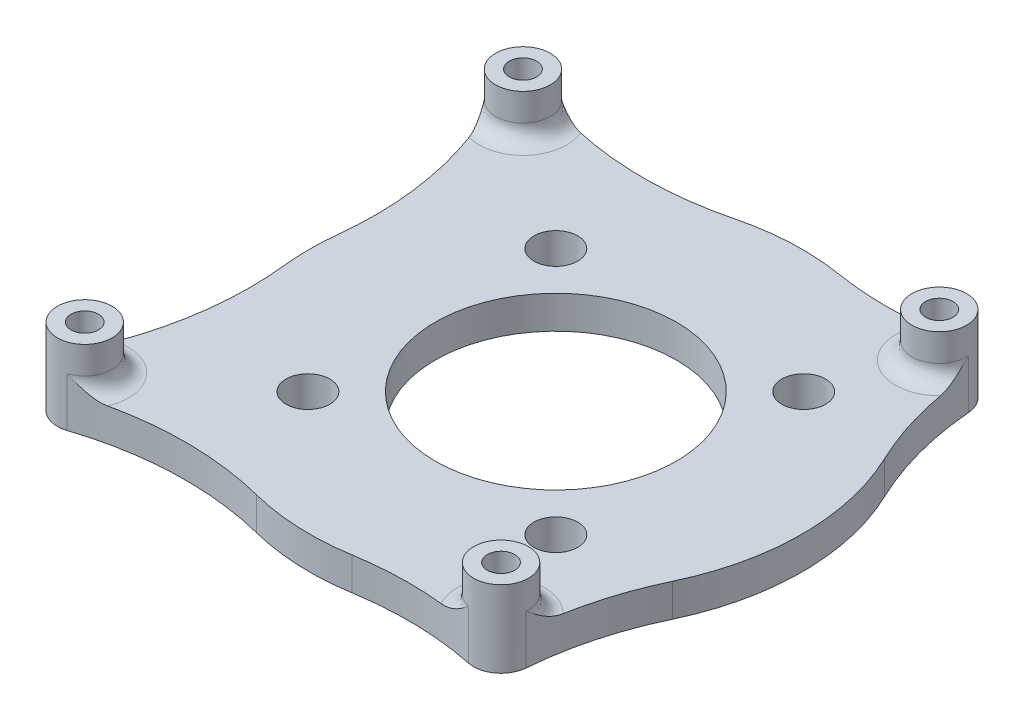
SolidWorks part; units mm, degrees
ref_plane "Front Plane" through (0, 0, 0) normal (0, 0, 1) x (1, 0, 0)
ref_plane "Top Plane" through (0, 0, 0) normal (0, 1, 0) x (1, 0, 0)
ref_plane "Right Plane" through (0, 0, 0) normal (1, 0, 0) x (0, 0, -1)
sketch "Sketch1" plane through (0, 0, 0) normal (0, 1, 0) x (1, 0, 0)
  line L0 (-23, 0) -> (15, 0) construction
  line L1 (-23, 20) -> (15, 20) construction
  line L2 (-23, 20) -> (-23, -20) construction
  line L3 (-23, -20) -> (15, -20) construction
  line L4 (15, 20) -> (15, -20) construction
  line L5 (-4, 20) -> (-4, -20) construction
  line L6 (0, 20) -> (0, -20) construction
  line L7 (-23, 20) -> (0, 0) construction
  line L8 (0, 0) -> (-23, -20) construction
  line L9 (15, 20) -> (0, 0) construction
  line L10 (0, 0) -> (15, -20) construction
  line L11 (-21.3596, 21.8865) -> (-15.233, 16.5591)
  line L12 (-11.3137, 11.3137) -> (0, 0) construction
  line L13 (15.4164, -16.3885) -> (17, -18.5)
  line L14 (17, 18.5) -> (15.4164, 16.3885)
  line L15 (-24.6404, 18.1135) -> (-18.5139, 12.7861)
  line L16 (2, 1.5) -> (17, -18.5) construction
  line L18 (13, 21.5) -> (11.4164, 19.3885)
  line L19 (11.4164, -19.3885) -> (13, -21.5)
  line L20 (-21.3596, 21.8865) -> (1.6404, 1.8865) construction
  line L22 (-24.6404, 18.1135) -> (-1.6404, -1.8865) construction
  line L23 (17, 18.5) -> (2, -1.5) construction
  line L24 (13, 21.5) -> (-2, 1.5) construction
  line L29 (-15.233, -16.5591) -> (-26.0573, -25.9715)
  line L31 (-18.5139, -12.7861) -> (-29.3382, -22.1985)
  circle A0 centre (0, 0) radius 16 construction
  circle A1 centre (-11.3137, 11.3137) radius 2
  circle A2 centre (11.3137, 11.3137) radius 2
  circle A3 centre (11.3137, -11.3137) radius 2
  circle A4 centre (-11.3137, -11.3137) radius 2
  circle A5 centre (0, 0) radius 11
  circle A6 centre (15, 20) radius 2.5
  circle A7 centre (-23, 20) radius 2.5
  circle A8 centre (-23, -20) radius 2.5
  circle A9 centre (15, -20) radius 2.5
  circle A10 centre (-23, 20) radius 1.75 construction
  circle A11 centre (-23, 20) radius 1.25
  circle A12 centre (15, 20) radius 1.75 construction
  circle A13 centre (15, 20) radius 1.25
  circle A14 centre (-23, -20) radius 1.75 construction
  circle A15 centre (-23, -20) radius 1.25
  circle A16 centre (15, -20) radius 1.75 construction
  circle A17 centre (15, -20) radius 1.25
  circle A19 centre (0, 0) radius 22.5
  point P14 (0, 0)
  dimension "D1" = 32
  dimension "D2" = 4
  dimension "D8" = 5
  dimension "D9" = 3.5
  dimension "D10" = 2.5
  dimension "D4" = 5
  dimension "D5" = 23
  dimension "D6" = 15
  dimension "D7" = 20
  dimension "D14" = 2.5
  dimension "D15" = 2.5
  dimension "D16" = 2.5
  dimension "D11" = 45
  dimension "D12" = 2.5
  dimension "D13" = 2.5
  dimension "D3" = 4
extrude "Boss-Extrude1" add sketch "Sketch1" along normal blind 3 contours A19 A1 A2 A3 A4 A5 | A19 L11 A7 L15 | A7 A11 | A6 A13 | A19 L14 A6 L18 | A19 L19 A9 L13 | A9 A17 | A19 L31 A8 L29 | A8 A15 | A19 L14 A6 | A19 A9 L13 region at (-19.2502, 0, -16.7393) region at (-20.7894, 0, -21.0072) region at (-2.3083, 0, -21.7414) region at (12.2573, 0, -19.5703) region at (15.7682, 0, -22.3046) region at (15.3554, 0, -17.2467) region at (-19.2502, 0, 16.7393) region at (-21.9928, 0, 17.7894) region at (12.2573, 0, 19.5703) region at (15.3554, 0, 17.2467) region at (12.5951, 0, 19.6564)
fillet "Fillet1" radius 30 8 edges at (11.4164, 1.5, -19.3885) (15.4164, 1.5, -16.3885) (15.4164, 1.5, 16.3885) (11.4164, 1.5, 19.3885) (-15.233, 1.5, 16.5591) (-15.233, 1.5, -16.5591) (-18.5139, 1.5, 12.7861) (-18.5139, 1.5, -12.7861)
sketch "Sketch2" plane through (0, 3, 0) normal (0, 1, 0) x (1, 0, 0)
  circle A0 centre (-23, 20) radius 2.5
  circle A1 centre (15, 20) radius 2.5
  circle A2 centre (15, -20) radius 2.5
  circle A3 centre (-23, -20) radius 2.5
  circle A4 centre (-23, 20) radius 1.25
  circle A5 centre (-23, 20) radius 1.25 construction
  circle A6 centre (15, 20) radius 1.25 construction
  circle A7 centre (-23, -20) radius 1.25 construction
  circle A8 centre (15, 20) radius 1.25
  circle A9 centre (-23, -20) radius 1.25
  circle A10 centre (15, -20) radius 1.25 construction
  circle A11 centre (15, -20) radius 1.25
  dimension "D1" = 5
extrude "Boss-Extrude2" add sketch "Sketch2" along normal blind 4
fillet "Fillet2" radius 1.5 4 edges at (-21.1135, 3, -18.3596) (-21.1135, 3, 18.3596) (13.5, 3, -18) (13.5, 3, 18)
sketch "Sketch3" plane through (0, 0, 0) normal (0, -1, 0) x (1, 0, 0)
  circle A1 centre (-23, -20) radius 1.75 construction
  circle A2 centre (15, -20) radius 1.75 construction
  circle A3 centre (15, 20) radius 1.75 construction
  circle A4 centre (-23, 20) radius 1.75 construction
  circle A5 centre (-23, -20) radius 1.75
  circle A6 centre (15, -20) radius 1.75
  circle A7 centre (15, 20) radius 1.75
  circle A8 centre (-23, 20) radius 1.75
extrude "Cut-Extrude1" cut sketch "Sketch3" against normal blind 3.5
equation "\"Ns\" = 33"
equation "\"Np\" = 45"
equation "\"Nr\" = 123"
equation "\"module\" = 0.5"
equation "\"num_planet\" = 3"
equation "\"pressure angle\" = 20.0"
equation "\"pressure_angle\" = 20.0"
equation "\"h_a\" = 0.5"
equation "\"h_b\" = 0.625"
equation "\"clr_tip_root\" = 0.125"
equation "\"h_f\" = 0.625"
equation "\"planet_bore\" = 10"
equation "\"motor_OD\" = 72"
equation "\"motor_height\" = 27"
equation "\"bearing_ID\" = 50"
equation "\"bearing_OD\" = 65"
equation "\"bearing_height\" = 7"
equation "\"clearance_planet\" = 1.5"
equation "\"sec_carrier_thickness\" = 5"
equation "\"sun_coupler_hub_thickness\" = 4"
equation "\"clearance_sun_coupler_sec_carrier\" = 1.5"
equation "\"clearance_motor_and_case\" = 5"
equation "\"case_mounting_surface_height\" = 4"
equation "\"Motor_case_thickness\" = 2.5"
equation "\"Motor_case_ID\" = 82"
equation "\"motor_case_OD_base\" = 87.0"
equation "\"case_mounting_hole_dia\" = 3"
equation "\"case_mounting_hole_shift\" = 1.0"
equation "\"case_mounting_PCD\" = 89.0"
equation "\"case_mounting_hole_allen_socket_dia\" = 5.5"
equation "\"clearance_case_mount_holes_shell_thickness\" = 1"
equation "\"Motor_case_OD_max\" = 96.5"
equation "\"base_plate_thickness\" = 4"
equation "\"dp_s\" = 16.5"
equation "\"db_s\" = 15.50492824296749"
equation "\"fw_s_calc\" = 1.2595130854287364"
equation "\"alpha_s\" = 0.8539582918412449"
equation "\"beta_s\" = 3.7466288708629643"
equation "\"dp_p\" = 22.5"
equation "\"db_p\" = 21.14308396768294"
equation "\"fw_p\" = 8.0"
equation "\"alpha_p\" = 0.8539582918412307"
equation "\"beta_p\" = 2.2920834163175385"
equation "\"dp_r\" = 61.5"
equation "\"db_r\" = 57.79109617833337"
equation "\"fw_r\" = 8.0"
equation "\"alpha_r\" = 0.8539582918412414"
equation "\"beta_r\" = 3.171331217828824"
equation "\"case_dist\" = 6.5"
equation "\"bearing mount thickness\" = 8"
equation "\"output_mounting_PCD\" = 73"
equation "\"carrier_PCD\" = 39.0"
equation "\"motor_mount_hole_PCD\" = 32"
equation "\"motor_mount_hole_dia\" = 4"
equation "\"motor_mount_hole_num\" = 4"
equation "\"motor_output_hole_PCD\" = 22"
equation "\"motor_output_hole_dia\" = 3"
equation "\"motor_output_hole_num\" = 4"
equation "\"motor_output_hole_CSK_OD\" = 6"
equation "\"motor_output_hole_CSK_head_height\" = 1.5"
equation "\"output_mounting_nut_thickness\" = 3.2"
equation "\"output_mounting_nut_depth\" = 3"
equation "\"output_mounting_nut_wrench_size\" = 7"
equation "\"output_mounting_hole_dia\" = 4"
equation "\"case_mounting_bolt_depth\" = 4.5"
equation "\"case_mounting_wrench_size\" = 5.5"
equation "\"case_mounting_nut_clearance\" = 2"
equation "\"case_mounting_nut_thickness\" = 2.4"
equation "\"central_hole_offset_from_motor_mount_PCD\" = 5"
equation "\"wire_slot_dist_from_center\" = 30"
equation "\"wire_slot_length\" = 10"
equation "\"wire_slot_radius\" = 2.5"
equation "\"driver_upper_holes_dist_from_center\" = 23"
equation "\"driver_lower_holes_dist_from_center\" = 15"
equation "\"driver_side_holes_dist_from_center\" = 20"
equation "\"driver_mount_holes_dia\" = 2.5"
equation "\"driver_mount_inserts_OD\" = 3.5"
equation "\"driver_mount_thickness\" = 1.5"
equation "\"driver_mount_height\" = 4"
equation "\"air_flow_hole_offset\" = 3"
equation "\"ring_radial_thickness\" = 5"
equation "\"ring_OD\" = 71.5"
equation "\"ring_to_chamfer_clearance\" = 2"
equation "\"Motor_case_OD_base_to_chamfer\" = 5"
equation "\"pattern_offset_from_motor_case_OD_base\" = 3"
equation "\"pattern_bulge_dia\" = 3"
equation "\"pattern_num_bulge\" = 18"
equation "\"pattern_depth\" = 2"
equation "\"planet_pin_bolt_dia\" = 5"
equation "\"planet_pin_socket_head_dia\" = 8.5"
equation "\"planet_shaft_dia\" = 8"
equation "\"planet_pin_bolt_wrench_size\" = 8"
equation "\"planet_shaft_step_offset\" = 1"
equation "\"planet_bearing_OD\" = 12"
equation "\"planet_bearing_width\" = 3.5"
equation "\"carrier_trapezoidal_support_sun_offset\" = 5"
equation "\"carrier_trapezoidal_support_hole_PCD_offset_bearing_ID\" = 4"
equation "\"carrier_trapezoidal_support_hole_dia\" = 3"
equation "\"carrier_trapezoidal_support_hole_socket_head_dia\" = 5.5"
equation "\"carrier_trapezoidal_support_hole_wrench_size\" = 5.5"
equation "\"carrier_bearing_step_width\" = 1.5"
equation "\"standard_clearance_1_5mm\" = 1.5"
equation "\"standard_fillet_1_5mm\" = 1.5"
equation "\"sun_shaft_bearing_OD\" = 16"
equation "\"sun_shaft_bearing_width\" = 5"
equation "\"sun_shaft_bearing_ID\" = 8"
equation "\"standard_bearing_insertion_chamfer\" = 0.5"
equation "\"sun_hub_dia\" = 31.0"
equation "\"sun_central_bolt_dia\" = 5"
equation "\"sun_central_bolt_socket_head_dia\" = 8.5"
equation "\"fw_s_used\" = 16.0"
equation "\"bearing_retainer_thickness\" = 2"
equation "\"tight_clearance_3DP\" = 0.4"
equation "\"loose_clearance_3DP\" = 0.8"
equation "\"D1@Sketch1\"= \"motor_mount_hole_PCD\""
equation "\"D2@Sketch1\"= \"motor_mount_hole_dia\""
equation "\"D3@Sketch1\"= \"motor_mount_hole_num\""
equation "\"D4@Sketch1\"= \"central_hole_offset_from_motor_mount_PCD\""
equation "\"D5@Sketch1\"= \"driver_upper_holes_dist_from_center\""
equation "\"D6@Sketch1\"= \"driver_lower_holes_dist_from_center\""
equation "\"D7@Sketch1\"= \"driver_side_holes_dist_from_center\""
equation "\"D8@Sketch1\"= \"driver_mount_inserts_OD\" + \"driver_mount_thickness\""
equation "\"D9@Sketch1\"= \"driver_mount_inserts_OD\""
equation "\"D10@Sketch1\"= \"driver_mount_holes_dia\""
equation "\"D13@Sketch1\"=(\"driver_mount_inserts_OD\" + \"driver_mount_thickness\")/2"
equation "\"D12@Sketch1\"=(\"driver_mount_inserts_OD\" + \"driver_mount_thickness\")/2"
equation "\"D14@Sketch1\"=(\"driver_mount_inserts_OD\" + \"driver_mount_thickness\")/2"
equation "\"D15@Sketch1\"=(\"driver_mount_inserts_OD\" + \"driver_mount_thickness\")/2"
equation "\"D16@Sketch1\"=(\"driver_mount_inserts_OD\" + \"driver_mount_thickness\")/2"
equation "\"D1@Boss-Extrude1\"=\"standard_clearance_1_5mm\"*2"
equation "\"D1@Sketch2\"= \"driver_mount_inserts_OD\" + \"driver_mount_thickness\""
equation "\"D1@Boss-Extrude2\"= \"driver_mount_height\""
equation "\"D1@Fillet2\"= \"standard_fillet_1_5mm\""
equation "\"D1@Cut-Extrude1\"= \"driver_mount_inserts_OD\""
equation "\"Np_b\"= 53"
equation "\"Np_s\"= 34"
equation "\"Nr_b\"= 125"
equation "\"Nr_s\"= 115"
equation "\"alpha_p_b\"= 0.8539582918412343"
equation "\"alpha_p_s\"= 0.8539582918412556"
equation "\"alpha_r_b\"= 0.8539582918412485"
equation "\"alpha_r_s\"= 0.8539582918412485"
equation "\"beta_p_b\"= 1.6883098314118712"
equation "\"beta_p_s\"= 3.586201063376312"
equation "\"beta_r_b\"= 3.147916583682497"
equation "\"beta_r_s\"= 3.2731339749868447"
equation "\"carrier_small_ring_inner_bearing_ID\"= 20"
equation "\"carrier_small_ring_inner_bearing_OD\"= 32"
equation "\"carrier_small_ring_inner_bearing_flap\"= 2"
equation "\"carrier_small_ring_inner_bearing_height\"= 7"
equation "\"carrier_thickness\"= 4"
equation "\"clr_tip_root_s\"= 0.15000000000000002"
equation "\"db_p_b\"= 34.8625962311572"
equation "\"db_p_s\"= 22.364684374704616"
equation "\"db_r_b\"= 70.47694655894313"
equation "\"db_r_s\"= 64.83879083422768"
equation "\"dp_p_b\"= 37.099999999999994"
equation "\"dp_p_s\"= 23.799999999999997"
equation "\"dp_r_b\"= 75.0"
equation "\"dp_r_s\"= 69.0"
equation "\"fw_p_b\"= 17.886889004287163"
equation "\"fw_p_s\"= 21.460611017453875"
equation "\"fw_r_b\"= 16.944245879236437"
equation "\"fw_r_s\"= 20.95020479116938"
equation "\"gear_casing_big_ring_to_bearing_dist\"= 32.950204791169384"
equation "\"gear_casing_thickness\"= 4"
equation "\"ring_OD_b\"= 85.0"
equation "\"small_ring_case_thickness\"= 4"
equation "\"small_ring_output_wall_thickness\"= 5"
equation "\"small_ring_output_wall_to_bearing_shaft_attachement_hole_CSK_OD\"= 8"
equation "\"small_ring_output_wall_to_bearing_shaft_attachement_hole_CSK_head_height\"= 2.0"
equation "\"small_ring_output_wall_to_bearing_shaft_attachement_hole_depth\"= 6.5"
equation "\"small_ring_output_wall_to_bearing_shaft_attachement_hole_dia\"= 4"
equation "\"small_ring_output_wall_to_bearing_shaft_attachement_hole_num\"= 3"
equation "\"small_ring_output_wall_to_bearing_shaft_attachement_hole_pcd\"= 12"
equation "\"small_ring_output_wall_to_bearing_shaft_attachement_nut_thickness\"= 3.2"
equation "\"small_ring_output_wall_to_bearing_shaft_attachement_nut_wrench\"= 7"
equation "\"bearing_mount_thickness\"= 8"
equation "\"stg1_stg2_mounting_pattern_width\" = 12"
equation "\"stg1_stg2_allen_socket_head_dia\" = 7.0"
equation "\"stg1_stg2_mounting_hole_dia\" = 4"
equation "\"Ns2\" = 33"
equation "\"Np2\" = 45"
equation "\"Nr2\" = 123"
equation "\"module2\" = 0.5"
equation "\"stg1_stg2_mounting_extra_width\" = 5.25"
equation "\"dp_s2\" = 16.5"
equation "\"db_s2\" = 15.50492824296749"
equation "\"fw_s_calc2\" = 5.95406185839039"
equation "\"alpha_s2\" = 0.8539582918412449"
equation "\"beta_s2\" = 3.7466288708629643"
equation "\"fw_s_used2\" = 16.0"
equation "\"fw_p2\" = 8.0"
